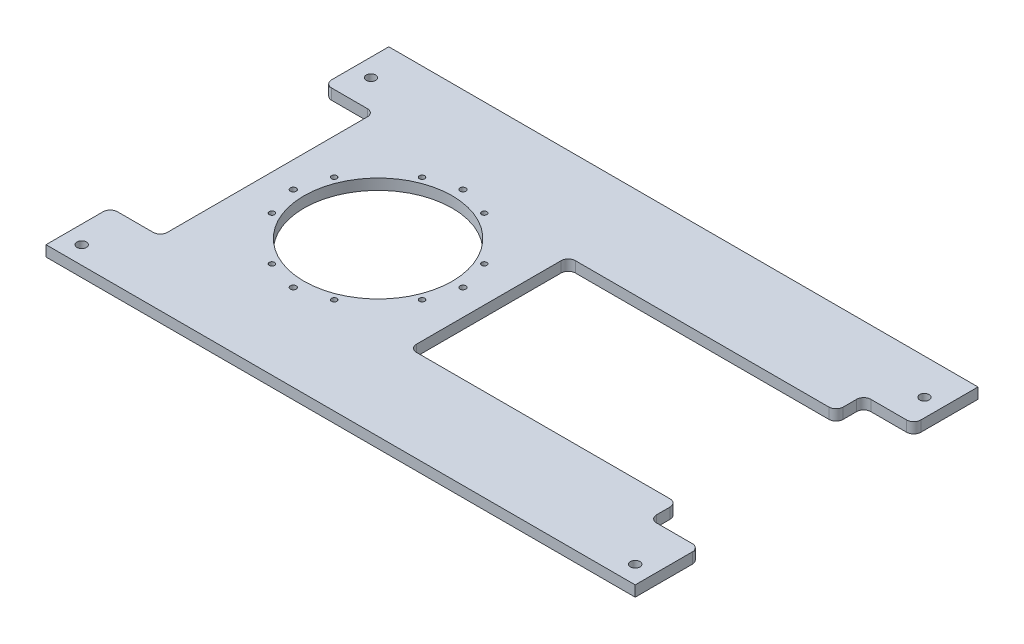
SolidWorks part; units mm, degrees
material "6061 Alloy"
ref_plane "Front Plane" through (0, 0, 0) normal (0, 0, 1) x (1, 0, 0)
ref_plane "Top Plane" through (0, 0, 0) normal (0, 1, 0) x (1, 0, 0)
ref_plane "Right Plane" through (0, 0, 0) normal (1, 0, 0) x (0, 0, -1)
sketch "Sketch1" plane through (0, 0, 0) normal (0, 1, 0) x (1, 0, 0)
  line L1 (0, 0) -> (330, 0)
  line L2 (0, 0) -> (0, 192)
  line L3 (0, 192) -> (330, 192)
  line L4 (330, 0) -> (330, 192)
  dimension "D1" = 192
  dimension "D2" = 330
extrude "Boss-Extrude1" add sketch "Sketch1" along normal blind 6
sketch "Sketch2" plane through (0, 6, 0) normal (0, 1, 0) x (1, 0, 0)
  line L0 (0, 0) -> (330, 0) construction
  line L1 (0, 0) -> (0, 192)
  line L2 (135.5, 96) -> (90, 96) construction
  line L3 (90, 96) -> (0, 96) construction
  line L4 (132.0365, 113.4121) -> (90, 96) construction
  circle A0 centre (90, 96) radius 50 construction
  circle A1 centre (90, 96) radius 45.5 construction
  circle A10 centre (132.0365, 113.4121) radius 1.5
  circle A11 centre (132.0365, 78.5879) radius 1.5
  circle A12 centre (107.4121, 53.9635) radius 1.5
  circle A13 centre (72.5879, 53.9635) radius 1.5
  circle A14 centre (47.9635, 78.5879) radius 1.5
  circle A15 centre (47.9635, 113.4121) radius 1.5
  circle A16 centre (72.5879, 138.0365) radius 1.5
  circle A17 centre (107.4121, 138.0365) radius 1.5
  point P21 (90, 96)
  point P30 (90, 96)
  dimension "D1" = 100
  dimension "D2" = 91
  dimension "D3" = 22.5
  dimension "D8" = 8
  dimension "D4" = 3
  dimension "D5" = 192
  dimension "D6" = 330
  dimension "D7" = 90
extrude "Cut-Extrude1" cut sketch "Sketch2" against normal through all and the other way through all contours A16 | A17 | A10 | A11 | A12 | A13 | A14 | A15
sketch "Sketch3" plane through (0, 6, 0) normal (0, 1, 0) x (1, 0, 0)
  line L0 (0, 0) -> (0, 192)
  line L1 (0, 0) -> (330, 0)
  line L2 (0, 0) -> (330, 0) construction
  circle A0 centre (90, 96) radius 41.5
  circle A1 centre (90, 96) radius 44 construction
  circle A5 centre (47.9635, 113.4121) radius 1.5 construction
  circle A6 centre (72.5879, 53.9635) radius 1.5 construction
  circle A7 centre (132.0365, 113.4121) radius 1.5 construction
  dimension "D1" = 83
  dimension "D2" = 330
  dimension "D3" = 192
extrude "Cut-Extrude2" cut sketch "Sketch3" against normal through all contours A0 region at (90, 6, -96)
hole_wizard "M5 Clearance Hole1" positions "Sketch13" profile "Sketch14" hole size "M5" standard "DIN"
sketch "Sketch13" plane through (0, 6, 0) normal (0, 1, 0) x (1, 0, 0)
  line L0 (0, 192) -> (0, 0) construction
  line L1 (330, 0) -> (330, 192) construction
  line L2 (10, 172) -> (320, 172) construction
  line L3 (320, 172) -> (320, 10) construction
  line L4 (320, 10) -> (10, 10) construction
  line L5 (10, 10) -> (10, 172) construction
  line L15 (330, 192) -> (0, 192) construction
  point P0 (10, 172)
  point P2 (10, 10)
  point P4 (320, 10)
  point P6 (320, 172)
  dimension "D1" = 10
  dimension "D2" = 10
  dimension "D3" = 10
  dimension "D4" = 10
  dimension "D5" = 162
  dimension "D6" = 162
  dimension "D7" = 20
sketch "Sketch14" plane through (10, 6, -172) normal (1, 0, 0) x (0, 0, 1)
  line L0 (0, 0) -> (0, 13.5323)
  line L1 (0, 13.5323) -> (2.65, 11.94)
  line L2 (2.65, 11.94) -> (2.65, 0)
  line L5 (2.65, 0) -> (0, 0)
  line L10 (0, 13.5323) -> (-2.65, 11.94) construction
  line L11 (0, -6.35) -> (0, 107.95) construction
  dimension "Hole Dia." = 5.3
  dimension "Hole Depth" = 11.94
  dimension "Drill Angle" = 118
hole_wizard "Tap Drill for M4 Tap1" positions "Sketch17" profile "Sketch18" hole size "M4" standard "DIN" end condition through all
sketch "Sketch17" plane through (0, 6, 0) normal (0, 1, 0) x (1, 0, 0)
  line L0 (132.0365, 113.4121) -> (132.0365, 78.5879)
  line L2 (132.0365, 96) -> (137.5, 96)
  line L3 (42.5, 96) -> (137.5, 96) construction
  circle A0 centre (90, 96) radius 47.5
  circle A1 centre (90, 96) radius 41.5 construction
  circle A3 centre (90, 96) radius 47.5 construction
  circle A6 centre (132.0365, 78.5879) radius 1.5 construction
  circle A7 centre (132.0365, 113.4121) radius 1.5 construction
  point P0 (137.5, 96)
  point P22 (90, 48.5)
  point P23 (42.5, 96)
  point P24 (90, 143.5)
  point P36 (0, 0)
  point P37 (116.3896, 135.4948)
  point P38 (0, 0)
  point P39 (0, 0)
  dimension "D1" = 95
  dimension "D2" = 4
sketch "Sketch18" plane through (137.5, 6, -96) normal (1, 0, 0) x (0, 0, 1)
  line L0 (0, 0) -> (0, 6)
  line L1 (0, 6) -> (1.65, 6)
  line L2 (1.65, 6) -> (1.65, 0)
  line L5 (1.65, 0) -> (0, 0)
  line L11 (0, -6.35) -> (0, 107.95) construction
  dimension "Thru Hole Dia." = 3.3
  dimension "Thru Hole Depth" = 6
sketch "Sketch19" plane through (0, 6, 0) normal (0, 1, 0) x (1, 0, 0)
  line L0 (0, 192) -> (0, 0) construction
  line L1 (0, 156) -> (28, 156)
  line L2 (0, 156) -> (0, 36)
  line L3 (0, 36) -> (28, 36)
  line L4 (28, 156) -> (28, 36)
  line L5 (330, 0) -> (330, 192) construction
  line L6 (330, 156) -> (302, 156)
  line L7 (330, 156) -> (330, 36)
  line L8 (330, 36) -> (302, 36)
  line L9 (302, 156) -> (302, 36)
  line L10 (0, 96) -> (28, 96) construction
  dimension "D1" = 120
  dimension "D2" = 28
extrude "Cut-Extrude3" cut sketch "Sketch19" against normal through all and the other way through all
sketch "Sketch21" plane through (0, 0, 0) normal (0, -1, 0) x (1, 0, 0)
  line L1 (302, -51.5) -> (152, -51.5)
  line L2 (302, -51.5) -> (302, -140.5)
  line L3 (302, -140.5) -> (152, -140.5)
  line L4 (152, -51.5) -> (152, -140.5)
  line L5 (302, -96) -> (302, -156) construction
  line L6 (302, -96) -> (302, -36) construction
  dimension "D1" = 150
  dimension "D2" = 89
extrude "Cut-Extrude4" cut sketch "Sketch21" against normal through all
fillet "Fillet1" radius 4 12 edges at (330, 3, -36) (302, 3, -36) (330, 3, -156) (302, 3, -156) (28, 3, -156) (28, 3, -36) (0, 3, -36) (0, 3, -156) (152, 3, -51.5) (152, 3, -140.5) (302, 3, -140.5) (302, 3, -51.5)
sketch "Sketch23" plane through (0, 0, 0) normal (0, 0, 1) x (1, 0, 0)
  line L0 (131.5, 6) -> (48.5, 6) construction
  line L1 (131.5, 6) -> (48.5, 6)
  point P2 (165, 3)
  point P3 (90, 6)
ref_axis "Axis1" through (90, 6, 0) along (0, 0, -1)
sketch "Sketch24" plane through (152, 0, 0) normal (1, 0, 0) x (0, 0, -1)
  line L0 (137.5, 6) -> (54.5, 6) construction
  line L1 (137.5, 6) -> (54.5, 6)
  point P2 (96, 3)
ref_axis "Axis2" through (152, 3, -96) along (-1, 0, 0)
equation "\"D2@Sketch13\"=\"D1@Sketch13\""
equation "\"D3@Sketch13\"=\"D1@Sketch13\""
equation "\"D4@Sketch13\"=\"D1@Sketch13\""
equation "\"D6@Sketch13\"=\"D5@Sketch13\""
